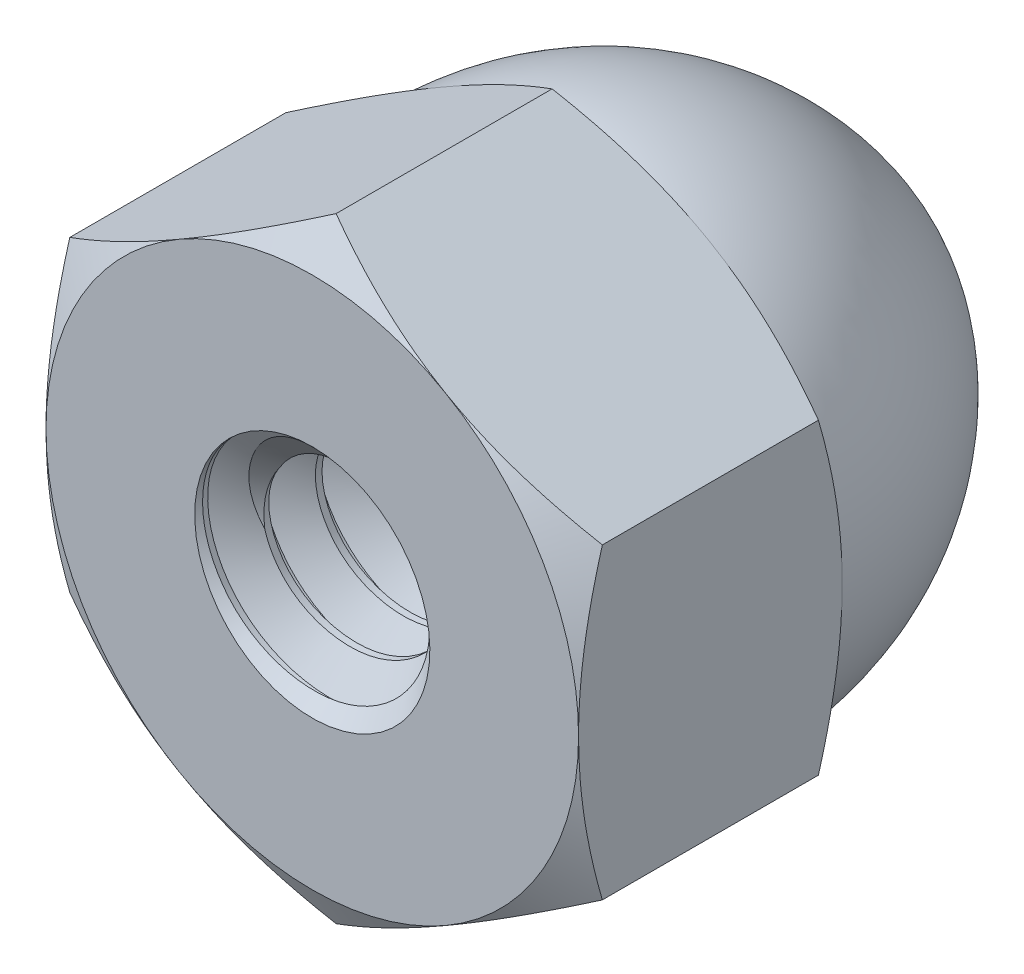
SolidWorks part; units mm, degrees
ref_plane "Front Plane" through (0, 0, 0) normal (0, 0, 1) x (1, 0, 0)
ref_plane "Top Plane" through (0, 0, 0) normal (0, 1, 0) x (1, 0, 0)
ref_plane "Right Plane" through (0, 0, 0) normal (1, 0, 0) x (0, 0, -1)
sketch "Sketch1" plane through (0, 0, 0) normal (0, 0, 1) x (1, 0, 0)
  line L1 (0, 4.5827) -> (-3.9688, 2.2914)
  line L2 (-3.9688, 2.2914) -> (-3.9688, -2.2914)
  line L3 (-3.9688, -2.2914) -> (0, -4.5827)
  line L4 (0, -4.5827) -> (3.9687, -2.2914)
  line L5 (3.9687, -2.2914) -> (3.9687, 2.2914)
  line L6 (3.9687, 2.2914) -> (0, 4.5827)
  circle A0 centre (0, 0) radius 3.9688 construction
  dimension "Hex" = 7.9375
extrude "Extrude1" add sketch "Sketch1" against normal blind 3.9291
sketch "Sketch2" plane through (0, 0, 0) normal (0, 0, 1) x (1, 0, 0)
  circle A0 centre (0, 0) radius 3.9688 construction
  circle A1 centre (0, 0) radius 3.9688
extrude "Cut-Extrude1" cut sketch "Sketch2" against normal through all draft 60 flip side to cut
sketch "Sketch3" plane through (0, 0, -3.9291) normal (0, 0, -1) x (-1, 0, 0)
  circle A1 centre (0, 0) radius 3.9688
  circle A2 centre (0, 0) radius 3.9688
  dimension "D1" = 0
extrude "Cut-Extrude2" cut sketch "Sketch3" against normal through all draft 60 flip side to cut
sketch "Sketch14" plane through (0, 0, 0) normal (1, 0, 0) x (0, 0, -1)
  line L0 (3.9291, 3.9688) -> (3.9291, 0)
  line L1 (3.9291, 0) -> (8.7312, 0)
  line L2 (3.9291, 0) -> (3.9291, 3.437) construction
  line L3 (3.9291, 3.9688) -> (12.6759, 3.9688) construction
  line L6 (0, 0) -> (3.9291, 0) construction
  arc A0 (3.9291, 3.9688) -> (8.7312, 0) centre (3.9291, -0.9209) cw
  dimension "overall length" = 8.7312
revolve "Revolve1" add sketch "Sketch14" angle 360 about L6
sketch "Sketch4" plane through (0, 0, 0) normal (0, 0, 1) x (1, 0, 0)
  circle A0 centre (0, 0) radius 1.7526
  dimension "Thread Dia" = 3.5052
extrude "Cut-Extrude3" cut sketch "Sketch4" against normal blind 3.9688
sketch "Sketch5" plane through (0, 0, 0) normal (0, 0, 1) x (1, 0, 0)
  circle A0 centre (0, 0) radius 1.7526 construction
  circle A1 centre (0, 0) radius 1.7526
sketch "Sketch15" plane through (0, 0, -3.9688) normal (0, 0, 1) x (1, 0, 0)
  circle A0 centre (0, 0) radius 1.7526 construction
  circle A1 centre (0, 0) radius 1.7526
curve "Helix/Spiral2" pitch 0.7937 height 7.1437 turns 9 parameters "pitch"=0.7937
sketch "Sketch18" plane through (0, 0, 0) normal (0, 0, 1) x (1, 0, 0)
  circle A0 centre (0, 0) radius 1.7526 construction
  circle A1 centre (0, 0) radius 1.7526
sketch "Sketch16" plane through (0, 0, 0) normal (1, 0, 0) x (0, 0, -1)
  line L0 (3.9688, 1.7526) -> (4.6633, 1.7526)
  line L1 (4.6633, 1.7526) -> (4.3656, 1.237)
  line L2 (4.3656, 1.237) -> (4.2664, 1.237)
  line L3 (4.2664, 1.237) -> (3.9688, 1.7526)
  line L4 (4.316, 1.237) -> (4.316, 1.7526) construction
  line L5 (4.1176, 1.4948) -> (4.5145, 1.4948) construction
  line L6 (3.9688, 1.7526) -> (3.9688, -1.7526) construction
  dimension "D1" = 60
  dimension "D2" = 0.0992
  dimension "D3" = 0.3969
sweep "Sweep1" add profiles "Sketch16" path "Helix/Spiral2"
sketch "Sketch17" plane through (0, 0, 0) normal (0, 0, 1) x (1, 0, 0)
  line L6 (0, 4.5827) -> (-3.9688, 2.2914)
  line L7 (-3.9688, 2.2914) -> (-3.9688, -2.2914)
  line L8 (-3.9688, -2.2914) -> (0, -4.5827)
  line L9 (0, -4.5827) -> (3.9687, -2.2914)
  line L10 (3.9687, -2.2914) -> (3.9687, 2.2914)
  line L11 (3.9687, 2.2914) -> (0, 4.5827)
  line L12 (0, 4.5827) -> (-3.9688, 2.2914)
  line L13 (-3.9688, 2.2914) -> (-3.9688, -2.2914)
  line L14 (-3.9688, -2.2914) -> (0, -4.5827)
  line L15 (0, -4.5827) -> (3.9687, -2.2914)
  line L16 (3.9687, -2.2914) -> (3.9687, 2.2914)
  line L17 (3.9687, 2.2914) -> (0, 4.5827)
  dimension "D1" = 0
extrude "Cut-Extrude8" cut sketch "Sketch17" along normal through all
extrude "Cut-Extrude9" cut sketch "Sketch18" against normal through all draft 45
sketch "Sketch20" plane through (0, 0, 0) normal (1, 0, 0) x (0, 0, -1)
  line L0 (4.3656, 1.7526) -> (5.3775, 0)
  line L1 (3.9688, 1.7526) -> (4.3656, 1.7526)
  line L2 (3.9688, 1.7526) -> (3.9688, 0)
  line L3 (3.9688, 1.7526) -> (4.6633, 1.7526) construction
  line L4 (3.9688, 1.7526) -> (3.9688, -1.7526) construction
  line L5 (3.9688, 0) -> (5.3775, 0)
  line L6 (0, 0) -> (-3.6507, 0) construction
  dimension "D1" = 0.3969
  dimension "D2" = 60
revolve "Cut-Revolve1" cut sketch "Sketch20" angle 360 about L6
equation "\"D2@Sketch16\" = \"pitch@Helix/Spiral2\"*.125"
equation "\"D3@Sketch16\" = \"pitch@Helix/Spiral2\"*.50"
equation "\"D1@Sketch20\" = \"pitch@Helix/Spiral2\"/2"
equation "\"D3@Helix/Spiral2\" = \"Thread Depth@Cut-Extrude3\"+.125"
equation "\"Nut Height@Extrude1\" = \"overall length@Sketch14\"*.45"
